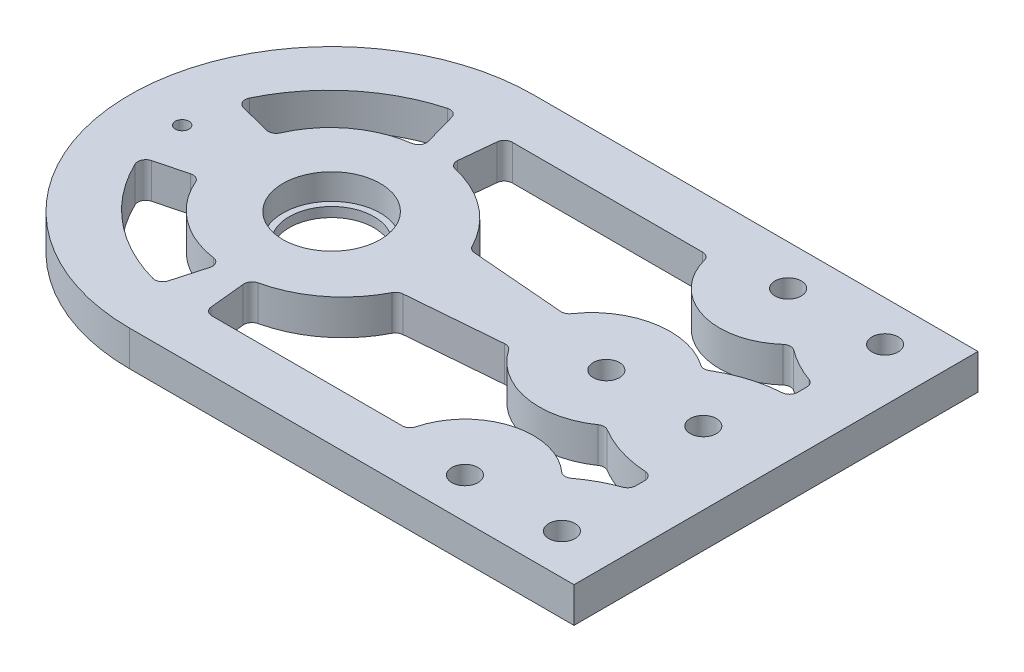
SolidWorks part; units mm, degrees
material "6061 Alloy"
ref_plane "Front Plane" through (0, 0, 0) normal (0, 0, 1) x (1, 0, 0)
ref_plane "Top Plane" through (0, 0, 0) normal (0, 1, 0) x (1, 0, 0)
ref_plane "Right Plane" through (0, 0, 0) normal (1, 0, 0) x (0, 0, -1)
sketch "Sketch1" plane through (0, 0, 0) normal (0, 1, 0) x (1, 0, 0)
  line L0 (-110, -100) -> (0, -100)
  line L1 (0, -100) -> (0, 0)
  line L2 (0, 0) -> (-110, 0)
  arc A0 (-110, 0) -> (-110, -100) centre (-110, -50) ccw
  circle A1 centre (-13, -10) radius 3.25
  circle A2 centre (-37, -10) radius 3.25
  circle A3 centre (-18, -50) radius 3.25
  circle A4 centre (-13, -90) radius 3.25
  circle A5 centre (-37, -90) radius 3.25
  circle A6 centre (-42, -50) radius 3.25
  circle A7 centre (-110, -50) radius 10.5
  dimension "D3" = 50
  dimension "D4" = 6.5
  dimension "D5" = 40
  dimension "D6" = 5
  dimension "D7" = 40
  dimension "D8" = 5
  dimension "D9" = 40
  dimension "D10" = 5
  dimension "D11" = 40
  dimension "D12" = 5
  dimension "D13" = 18
  dimension "D14" = 50
  dimension "D15" = 24
  dimension "D16" = 10
  dimension "D17" = 21
  dimension "D1" = 100
  dimension "D2" = 110
extrude "Boss-Extrude1" add sketch "Sketch1" along normal blind 8.7312
sketch "Sketch2" plane through (0, 8.7312, 0) normal (0, 1, 0) x (1, 0, 0)
  circle A0 centre (-110, -50) radius 12.05
  dimension "D1" = 24.1
extrude "Cut-Extrude1" cut sketch "Sketch2" against normal blind 6.35
ref_plane "Plane1" through (0, 1.1906, 0) normal (0, -1, 0) x (-1, 0, 0)
ref_plane "Plane2" through (0, 4.3656, 0) normal (0, -1, 0) x (-1, 0, 0)
ref_plane "Plane3" through (-110, 0, 0) normal (1, 0, 0) x (0, 0, -1)
ref_axis "Axis1" through (-110, 4.3656, 105) along (0, 0, -1)
ref_plane "Plane5" through (0, 0, 50) normal (0, 0, 1) x (1, 0, 0)
sketch "Sketch6" plane through (0, 8.7312, 0) normal (0, 1, 0) x (1, 0, 0)
  line L4 (-109.3685, -50) -> (-49.4223, -50) construction
  line L5 (0, 0) -> (-110, 0) construction
  line L6 (-133.7939, -41.071) -> (-145.4778, -38.0518)
  line L7 (-115.8698, -13.0563) -> (-112.4178, -25.2713)
  line L8 (-105.5137, -25.2713) -> (-104.2588, -12.7954)
  line L9 (-104.2588, -12.7954) -> (-53.7346, -12.7954)
  line L11 (-59.0327, -43.1802) -> (-84.6627, -41.071)
  line L12 (-13.5562, -27.3664) -> (-13.5562, -33.0289)
  line L13 (-115.8698, -86.9437) -> (-112.4178, -74.7287)
  line L14 (-133.7939, -58.929) -> (-145.4778, -61.9482)
  line L15 (-104.2588, -87.2046) -> (-53.7346, -87.2046)
  line L16 (-105.5137, -74.7287) -> (-104.2588, -87.2046)
  line L17 (-59.0327, -56.8198) -> (-84.6627, -58.929)
  line L18 (-13.5562, -72.6336) -> (-13.5562, -66.9711)
  arc A4 (-145.4778, -38.0518) -> (-115.8698, -13.0563) centre (-106.6352, -54.0285) cw
  arc A5 (-112.4178, -25.2713) -> (-133.7939, -41.071) centre (-111.4199, -48.9815) ccw
  arc A6 (-53.7346, -12.7954) -> (-24.4627, -21.4314) centre (-37, -10) ccw
  arc A7 (-24.4627, -21.4314) -> (-13.5562, -27.3664) centre (-4.2469, 2.7299) ccw
  arc A9 (-30.2643, -38.0518) -> (-59.0327, -43.1802) centre (-42.4007, -53.2252) ccw
  arc A10 (-84.6627, -41.071) -> (-105.5137, -25.2713) centre (-109.9332, -52.7621) ccw
  circle A11 centre (-42, -50) radius 3.25 construction
  arc A12 (-13.5562, -33.0289) -> (-30.2643, -38.0518) centre (-13.5562, -63.3292) ccw
  arc A13 (-145.4778, -61.9482) -> (-115.8698, -86.9437) centre (-106.6352, -45.9715) ccw
  arc A14 (-112.4178, -74.7287) -> (-133.7939, -58.929) centre (-111.4199, -51.0185) cw
  arc A15 (-24.4627, -78.5686) -> (-13.5562, -72.6336) centre (-4.2469, -102.7299) cw
  arc A16 (-53.7346, -87.2046) -> (-24.4627, -78.5686) centre (-37, -90) cw
  arc A17 (-84.6627, -58.929) -> (-105.5137, -74.7287) centre (-109.9332, -47.2379) cw
  arc A18 (-30.2643, -61.9482) -> (-59.0327, -56.8198) centre (-42.4007, -46.7748) cw
  arc A19 (-13.5562, -66.9711) -> (-30.2643, -61.9482) centre (-13.5562, -36.6708) cw
  circle A20 centre (-147, -50) radius 1.7
  arc A21 (-110, 0) -> (-110, -100) centre (-110, -50) ccw construction
  dimension "D2" = 42
  dimension "D3" = 3.4
  dimension "D1" = 50
  dimension "D4" = 37
extrude "Cut-Extrude4" cut sketch "Sketch6" against normal through all
fillet "Fillet1" radius 2 26 edges at (-84.6627, 4.3656, 41.071) (-59.0327, 4.3656, 43.1802) (-13.5562, 4.3656, 33.0289) (-30.2643, 4.3656, 38.0518) (-24.4627, 4.3656, 78.5686) (-53.7346, 4.3656, 87.2046) (-13.5562, 4.3656, 72.6336) (-13.5562, 4.3656, 66.9711) (-30.2643, 4.3656, 61.9482) (-59.0327, 4.3656, 56.8198) (-104.2588, 4.3656, 87.2046) (-84.6627, 4.3656, 58.929) (-105.5137, 4.3656, 74.7287) (-133.7939, 4.3656, 41.071) (-112.4178, 4.3656, 25.2713) (-115.8698, 4.3656, 13.0563) (-145.4778, 4.3656, 38.0518) (-115.8698, 4.3656, 86.9437) (-112.4178, 4.3656, 74.7287) (-133.7939, 4.3656, 58.929) (-145.4778, 4.3656, 61.9482) (-13.5562, 4.3656, 27.3664) (-24.4627, 4.3656, 21.4314) (-53.7346, 4.3656, 12.7954) (-104.2588, 4.3656, 12.7954) (-105.5137, 4.3656, 25.2713)
